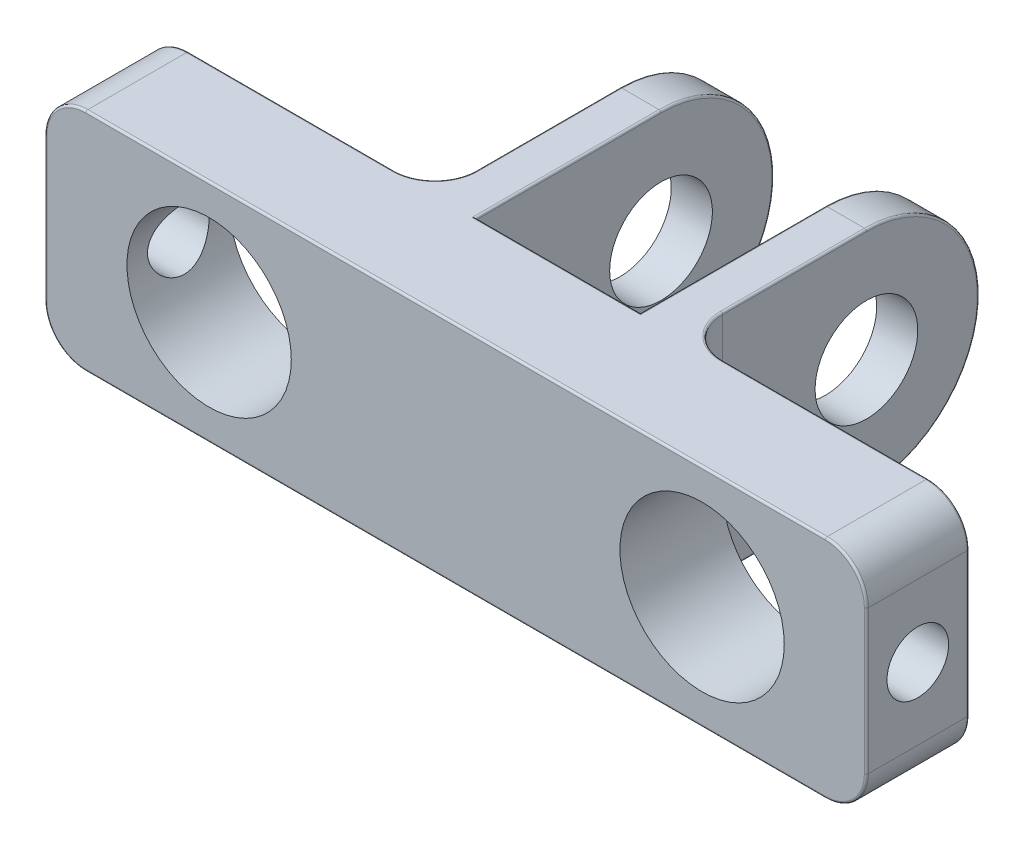
SolidWorks part; units mm, degrees
ref_plane "Front Plane" through (0, 0, 0) normal (0, 0, 1) x (1, 0, 0)
ref_plane "Top Plane" through (0, 0, 0) normal (0, 1, 0) x (1, 0, 0)
ref_plane "Right Plane" through (0, 0, 0) normal (1, 0, 0) x (0, 0, -1)
sketch "Sketch1" plane through (0, 0, 0) normal (0, 0, 1) x (1, 0, 0)
  line L1 (-457.2, 139.7) -> (457.2, 139.7)
  line L2 (-508, 88.9) -> (-508, -88.9)
  line L3 (-457.2, -139.7) -> (457.2, -139.7)
  line L4 (508, 88.9) -> (508, -88.9)
  line L5 (-508, 139.7) -> (508, -139.7) construction
  line L6 (-508, -139.7) -> (508, 139.7) construction
  arc A0 (457.2, 139.7) -> (508, 88.9) centre (457.2, 88.9) cw
  arc A1 (457.2, -139.7) -> (508, -88.9) centre (457.2, -88.9) ccw
  arc A2 (-508, -88.9) -> (-457.2, -139.7) centre (-457.2, -88.9) ccw
  arc A3 (-457.2, 139.7) -> (-508, 88.9) centre (-457.2, 88.9) ccw
  point P0 (0, 0)
  dimension "D3" = 50.8
  dimension "D1" = 1016
  dimension "D2" = 279.4
extrude "Boss-Extrude1" add sketch "Sketch1" along normal blind 127
sketch "Sketch2" plane through (0, 0, 127) normal (0, 0, 1) x (1, 0, 0)
  line L0 (-508, 88.9) -> (-508, -88.9) construction
  line L1 (508, -88.9) -> (508, 88.9) construction
  circle A0 centre (-304.8, 0) radius 101.6
  circle A1 centre (304.8, 0) radius 101.6
  dimension "D1" = 203.2
  dimension "D2" = 203.2
  dimension "D3" = 203.2
extrude "Cut-Extrude1" cut sketch "Sketch2" against normal blind 127
sketch "Sketch3" plane through (508, 0, 0) normal (1, 0, 0) x (0, 0, -1)
  line L0 (-127, 139.7) -> (0, 139.7) construction
  circle A0 centre (-63.5, 0) radius 38.1
  dimension "D1" = 76.2
  dimension "D2" = 63.5
  dimension "D3" = 139.7
extrude "Cut-Extrude2" cut sketch "Sketch3" against normal blind 127
mirror "Mirror1" about plane through (0, 0, 0) normal (1, 0, 0) of "Cut-Extrude2"
sketch "Sketch9" plane through (0, 0, 0) normal (1, 0, 0) x (0, 0, -1)
  line L0 (0, -88.9) -> (0, 88.9) construction
  line L1 (0, -88.9) -> (0, 88.9)
  line L2 (0, 88.9) -> (0, 139.7) construction
  line L3 (0, 88.9) -> (0, 139.7)
  line L4 (0, -139.7) -> (0, -88.9) construction
  line L5 (0, -139.7) -> (0, -88.9)
  line L6 (-127, 0) -> (228.6, 0) construction
  line L7 (-127, -88.9) -> (-127, 88.9) construction
  line L8 (0, 139.7) -> (228.6, 139.7)
  line L9 (0, -139.7) -> (228.6, -139.7)
  arc A0 (228.6, -139.7) -> (228.6, 139.7) centre (228.6, 0) ccw
  circle A1 centre (228.6, 0) radius 63.5
  point P9 (0, 0)
  point P13 (0, 0)
  point P15 (0, 0)
  dimension "D2" = 279.4
  dimension "D3" = 127
  dimension "D1" = 355.6
extrude "Boss-Extrude2" add sketch "Sketch9" along normal mid plane 304.8
sketch "Sketch11" plane through (0, 139.7, 0) normal (0, 1, 0) x (1, 0, 0)
  line L0 (152.4, 368.3) -> (-152.4, 368.3) construction
  line L1 (-101.6, 368.3) -> (101.6, 368.3)
  line L2 (-101.6, 368.3) -> (-101.6, 0)
  line L3 (-101.6, 0) -> (101.6, 0)
  line L4 (101.6, 368.3) -> (101.6, 0)
  line L5 (0, 0) -> (0, 368.3) construction
  dimension "D1" = 101.6
  dimension "D2" = 101.6
extrude "Cut-Extrude3" cut sketch "Sketch11" against normal through all both and the other way through all
fillet "Fillet1" radius 50.8 2 edges at (152.4, 0, 0) (-152.4, 0, 0)
fillet "Fillet2" radius 2.54 36 edges at (-101.6, 139.7, -114.3) (-101.6, -139.7, -114.3) (101.6, -139.7, -114.3) (101.6, 139.7, -114.3) (493.121, 124.821, 127) (508, 0, 127) (493.121, -124.821, 127) (0, -139.7, 127) (-493.121, -124.821, 127) (-508, 0, 127) (-493.121, 124.821, 127) (493.121, 124.821, 0) (508, 0, 0) (493.121, -124.821, 0) (330.2, -139.7, 0) (167.279, -139.7, -14.879) (152.4, -139.7, -139.7) (152.4, 0, -368.3) (152.4, 139.7, -139.7) (167.279, 139.7, -14.879) (-167.279, 139.7, -14.879) (-152.4, 139.7, -139.7) (-152.4, 0, -368.3) (-152.4, -139.7, -139.7) (-167.279, -139.7, -14.879) (-330.2, -139.7, 0) (-493.121, -124.821, 0) (-508, 0, 0) (-493.121, 124.821, 0) (-101.6, 0, -368.3) (101.6, 0, -368.3) (0, -139.7, 0) (0, 139.7, 0) (0, 139.7, 127) (330.2, 139.7, 0) (-330.2, 139.7, 0)
